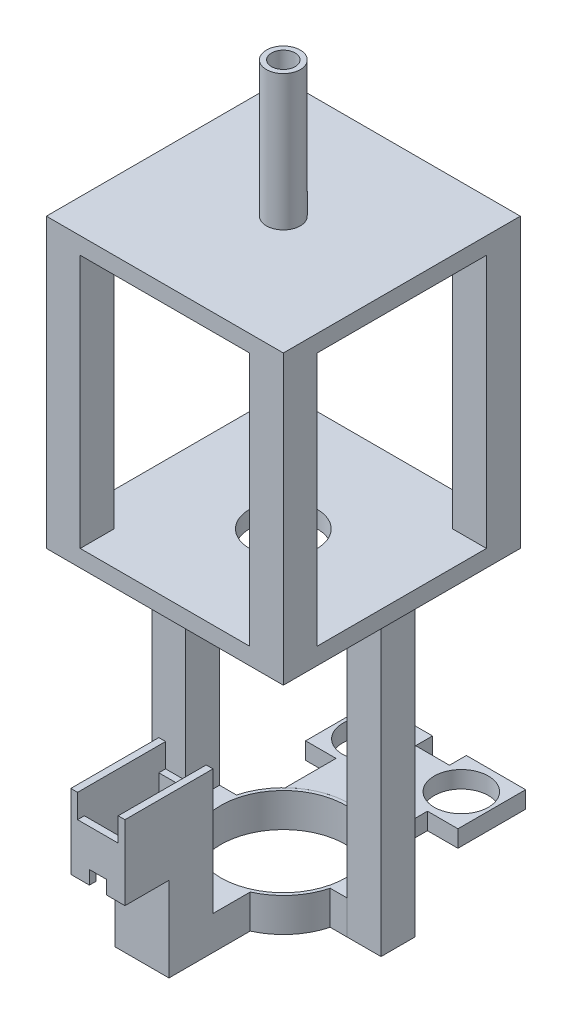
SolidWorks part; units mm, degrees
ref_plane "Front Plane" through (0, 0, 0) normal (0, 0, 1) x (1, 0, 0)
ref_plane "Top Plane" through (0, 0, 0) normal (0, 1, 0) x (1, 0, 0)
ref_plane "Right Plane" through (0, 0, 0) normal (1, 0, 0) x (0, 0, -1)
sketch "Sketch2" plane through (0, 0, 0) normal (0, 1, 0) x (1, 0, 0)
  line L0 (0, 18.5) -> (0, -18.5) construction
  line L1 (-18.5, 0) -> (18.5, 0) construction
  line L2 (0, -5) -> (0, 5) construction
  line L3 (-18.8481, 5) -> (-33.8481, 5)
  line L4 (-33.8481, 5) -> (-33.8481, -5)
  line L5 (-33.8481, -5) -> (-18.8481, -5)
  line L6 (33.8481, -5) -> (18.8481, -5)
  line L7 (33.8481, 5) -> (33.8481, -5)
  line L8 (18.8481, 5) -> (33.8481, 5)
  line L9 (0, 29.0712) -> (22.5, 29.0712)
  line L10 (22.5, 29.0712) -> (22.5, 49.0712)
  line L11 (22.5, 49.0712) -> (5, 49.0712)
  line L12 (-22.5, 49.0712) -> (-22.5, 29.0712)
  line L13 (-22.5, 29.0712) -> (0, 29.0712)
  line L14 (22.5, 39.0712) -> (21.5, 39.0712) construction
  line L20 (-5, 49.0712) -> (-22.5, 49.0712)
  line L21 (0, 44.0712) -> (0, 29.0712) construction
  line L22 (-5, 49.0712) -> (-5, 44.0712)
  line L23 (-5, 44.0712) -> (5, 44.0712)
  line L24 (5, 44.0712) -> (5, 49.0712)
  line L25 (13.5, 47.0712) -> (13.5, 49.0712) construction
  line L26 (13.5, 31.0712) -> (13.5, 29.0712) construction
  line L27 (-13.5, 39.0712) -> (13.5, 39.0712) construction
  line L28 (-13.5, 14.0712) -> (-13.5, 29.0712)
  line L29 (13.5, 29.0712) -> (13.5, 14.0712)
  line L30 (-8, -19.5) -> (8, -19.5) construction
  line L31 (-8, -17.7834) -> (-8, -41.7834)
  line L32 (-8, -41.7834) -> (8, -41.7834)
  line L33 (8, -41.7834) -> (8, -17.7834)
  line L34 (-18.8481, 5) -> (-23.8481, 5) construction
  line L35 (-5.5, -19.5) -> (5.5, -19.5) construction
  line L36 (-23.8481, 5) -> (-23.8481, -5)
  line L37 (23.8481, 5) -> (23.8481, -5)
  circle A0 centre (0, 0) radius 18.5
  circle A1 centre (0, 0) radius 19.5
  circle A2 centre (13.5, 39.0712) radius 8
  circle A3 centre (-13.5, 39.0712) radius 8
  point P9 (0, 0)
  point P45 (0, -19.5)
  point P54 (0, -19.5)
  dimension "D1" = 37
  dimension "D2" = 5
  dimension "D4" = 39
  dimension "D8" = 1
  dimension "D9" = 16
  dimension "D3" = 10
  dimension "D5" = 5
  dimension "D6" = 20
  dimension "D7" = 45
  dimension "D10" = 17.5
  dimension "D11" = 15
  dimension "D12" = 27
  dimension "D13" = 15
  dimension "D14" = 16
  dimension "D15" = 24
  dimension "D16" = 5
extrude "Connector sleeve" add sketch "Sketch2" along normal blind 5 and the other way blind 5 contours A1 A0 | A1 A0 | A1 A0 | A1 A0 region at (-16.3228, 0, -9.6234)
ref_plane "Plane2" through (0, 30, 0) normal (0, 1, 0) x (1, 0, 0)
extrude "Sensor holder" add sketch "Sketch2<10>" along normal blind 5 separate body contours L24 L23 L22 L20 L12 L13 L9 L10 L11 A2 A3 | A1 L29 L9 L13 L28 region at (0, 0, -23.3278) region at (0, 0, -38.234)
sketch "Sketch2<10>" plane through (0, 0, 0) normal (0, 1, 0) x (1, 0, 0) same geometry as "Sketch2"
extrude "Arms" add sketch "Sketch2<18>" along normal blind 85 from offset 5 contours L36 L3 L4 L5 | L8 L37 L6 L7 region at (-28.8481, 0, 0) region at (28.8481, 0, 0) offset against normal yes
sketch "Sketch2<18>" plane through (0, 0, 0) normal (0, 1, 0) x (1, 0, 0) same geometry as "Sketch2"
extrude "Arms2" add sketch "Sketch2<22>" along normal blind 10 from offset 5 contours A1 L3 L4 L5 | A1 L6 L7 L8 | A1 L3 L36 L5 | A1 L6 L37 L8 region at (-21.562, 0, 0) region at (-28.8481, 0, 0) region at (21.562, 0, 0) region at (28.8481, 0, 0) offset against normal yes
sketch "Sketch2<22>" plane through (0, 0, 0) normal (0, 1, 0) x (1, 0, 0) same geometry as "Sketch2"
extrude "Servoholder" add sketch "Sketch2<21>" along normal blind 10 from offset 5 contours A1 L31 L32 L33 region at (0, 0, 30.3552) offset against normal yes
sketch "Sketch2<21>" plane through (0, 0, 0) normal (0, 1, 0) x (1, 0, 0) same geometry as "Sketch2"
sketch "Sketch31" plane through (0, 5, 0) normal (0, 1, 0) x (1, 0, 0)
  line L0 (-8, -41.7834) -> (-8, -28.7834)
  line L1 (-8, -17.7834) -> (-8, -41.7834) construction
  line L2 (-8, -28.7834) -> (8, -28.7834)
  line L3 (8, -41.7834) -> (8, -17.7834) construction
  line L4 (8, -28.7834) -> (8, -41.7834)
  line L5 (8, -41.7834) -> (-8, -41.7834)
  dimension "D1" = 13
extrude "Servoholder2" add sketch "Sketch31" along normal blind 15
sketch "Sketch33" plane through (0, 20, 0) normal (0, 1, 0) x (1, 0, 0)
  line L0 (0, -28.7834) -> (0, -30.7834) construction
  line L1 (8, -28.7834) -> (-8, -28.7834) construction
  line L2 (-8, -41.7834) -> (8, -41.7834) construction
  line L4 (8, -28.7834) -> (-8, -28.7834) construction
  line L6 (-8, -28.7834) -> (-8, -54.7834)
  line L7 (-8, -54.7834) -> (8, -54.7834)
  line L8 (8, -54.7834) -> (8, -28.7834)
  line L9 (0, -41.7834) -> (6, -41.7834) construction
  line L10 (0, -54.7834) -> (0, -52.7834) construction
  line L11 (-6, -52.7834) -> (6, -52.7834)
  line L12 (6, -52.7834) -> (6, -30.7834)
  line L13 (6, -30.7834) -> (-6, -30.7834)
  line L14 (-6, -52.7834) -> (-6, -30.7834)
  line L15 (-8, -28.7834) -> (8, -28.7834)
  dimension "D1" = 8
  dimension "D2" = 26
  dimension "D3" = 6
  dimension "D4" = 2
  dimension "D5" = 2
extrude "Servoholder3" add sketch "Sketch33" along normal blind 22
sketch "Servoholder4" plane through (0, 42, 0) normal (0, 1, 0) x (1, 0, 0)
  line L0 (-6, -30.7834) -> (-6, -28.7834)
  line L1 (8, -28.7834) -> (-8, -28.7834) construction
  line L2 (-6, -28.7834) -> (6, -28.7834)
  line L3 (8, -28.7834) -> (-8, -28.7834) construction
  line L4 (6, -28.7834) -> (6, -30.7834)
  line L5 (6, -30.7834) -> (-6, -30.7834)
  line L6 (-6, -41.7834) -> (6, -41.7834) construction
  line L7 (-6, -30.7834) -> (-6, -52.7834) construction
  line L8 (6, -52.7834) -> (6, -30.7834) construction
  line L9 (6, -54.7834) -> (6, -52.7834)
  line L10 (-6, -52.7834) -> (-6, -54.7834)
  line L11 (-6, -54.7834) -> (6, -54.7834)
  line L12 (6, -52.7834) -> (-6, -52.7834)
extrude "Servogrooves" cut sketch "Servoholder4" against normal blind 7
sketch "Sketch36" plane through (0, 0, 54.7834) normal (0, 0, 1) x (1, 0, 0)
  line L0 (0, 20) -> (0, 24) construction
  line L1 (-8, 20) -> (8, 20) construction
  line L2 (-2.5, 24) -> (2.5, 24)
  line L3 (-2.5, 24) -> (-2.5, 20)
  line L4 (-6, 20) -> (6, 20) construction
  line L5 (2.5, 24) -> (2.5, 20)
  line L6 (2.5, 20) -> (-2.5, 20)
  point P8 (0, 24)
  dimension "D1" = 4
  dimension "D2" = 2.5
extrude "Servowiring" cut sketch "Sketch36" against normal blind 2
sketch "Sketch4" plane through (0, 80, 0) normal (0, 1, 0) x (1, 0, 0)
  line L1 (-35, -35) -> (35, -35)
  line L2 (-35, -35) -> (-35, 35)
  line L3 (-35, 35) -> (35, 35)
  line L4 (35, -35) -> (35, 35)
  line L5 (-35, -35) -> (35, 35) construction
  line L6 (-35, 35) -> (35, -35) construction
  circle A0 centre (0, 0) radius 10
  point P0 (0, 0)
  dimension "D2" = 20
  dimension "D1" = 70
extrude "Motor enclosure" add sketch "Sketch4" along normal blind 5
sketch "Sketch6" plane through (0, 85, 0) normal (0, 1, 0) x (1, 0, 0)
  line L0 (-35, 35) -> (-25, 35)
  line L1 (35, 35) -> (-35, 35) construction
  line L2 (-25, 35) -> (-25, 25)
  line L3 (-25, 25) -> (-35, 25)
  line L4 (-35, 35) -> (-35, -35) construction
  line L5 (-35, 25) -> (-35, 35)
  line L6 (0, 35) -> (0, -35) construction
  line L7 (-35, -35) -> (35, -35) construction
  line L8 (-35, 0) -> (35, 0) construction
  line L9 (35, -35) -> (35, 35) construction
  line L10 (25, 25) -> (35, 25)
  line L11 (35, 25) -> (35, 35)
  line L12 (35, 35) -> (25, 35)
  line L13 (25, 35) -> (25, 25)
  line L14 (25, -25) -> (35, -25)
  line L15 (35, -25) -> (35, -35)
  line L16 (35, -35) -> (25, -35)
  line L17 (25, -35) -> (25, -25)
  line L18 (-25, -25) -> (-35, -25)
  line L19 (-25, -35) -> (-25, -25)
  line L20 (-35, -25) -> (-35, -35)
  line L21 (-35, -35) -> (-25, -35)
  dimension "D2" = 10
extrude "Motor enclosure 2" add sketch "Sketch6" along normal blind 75
sketch "Sketch7" plane through (0, 160, 0) normal (0, 1, 0) x (1, 0, 0)
  line L0 (-35, 35) -> (35, 35)
  line L1 (35, 35) -> (35, -35)
  line L2 (35, -35) -> (-35, -35)
  line L3 (-35, -25) -> (-35, -35) construction
  line L4 (-35, -35) -> (-35, 35)
extrude "Motor enclosure 3" add sketch "Sketch7" along normal blind 5 contours L1 L2 L4 L0
sketch "Sketch8" plane through (0, 165, 0) normal (0, 1, 0) x (1, 0, 0)
  circle A0 centre (0, 0) radius 5
  point P0 (0, 0)
  dimension "D1" = 10
extrude "Connector" add sketch "Sketch8" along normal blind 40
sketch "Sketch26" plane through (0, 205, 0) normal (0, 1, 0) x (1, 0, 0)
  circle A0 centre (0, 0) radius 3.5
  dimension "D1" = 7
extrude "Cut-Extrude1" cut sketch "Sketch26" against normal up to next (45 mm away)
